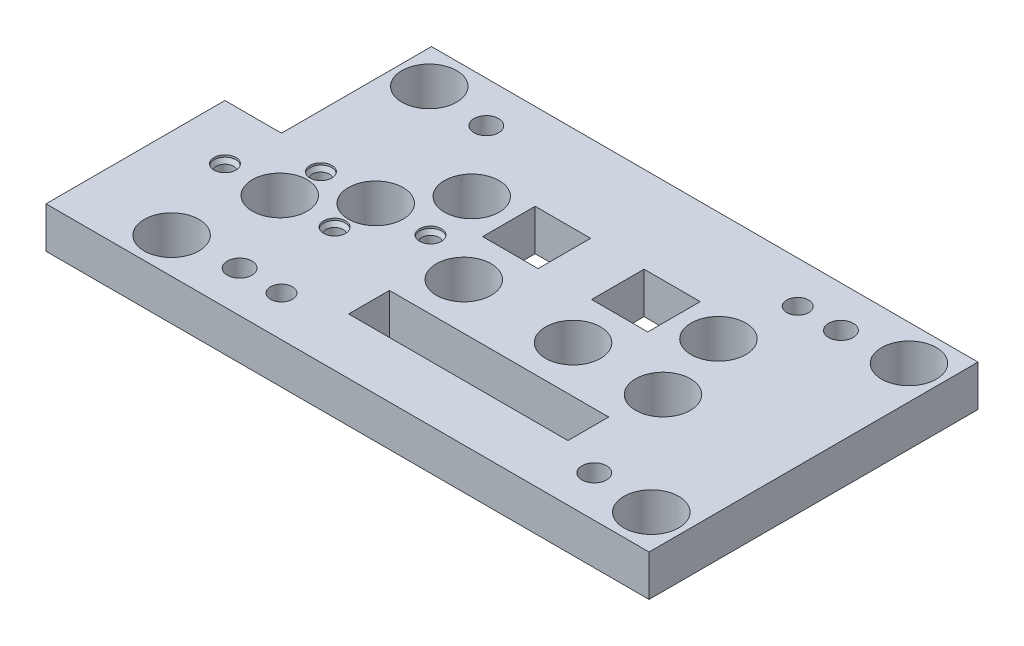
SolidWorks part; units mm, degrees
material "Plain Carbon Steel"
ref_plane "Front Plane" through (0, 0, 0) normal (0, 0, 1) x (1, 0, 0)
ref_plane "Top Plane" through (0, 0, 0) normal (0, 1, 0) x (1, 0, 0)
ref_plane "Right Plane" through (0, 0, 0) normal (1, 0, 0) x (0, 0, -1)
sketch "Sketch1" plane through (0, 0, 0) normal (0, 1, 0) x (1, 0, 0)
  line L1 (-110, -60) -> (110, -60)
  line L2 (-110, -60) -> (-110, 60)
  line L3 (-110, 60) -> (110, 60)
  line L4 (110, -60) -> (110, 60)
  line L5 (-110, -60) -> (110, 60) construction
  line L6 (-110, 60) -> (110, -60) construction
  point P0 (0, 0)
  dimension "D1" = 120
  dimension "D2" = 220
extrude "Boss-Extrude1" add sketch "Sketch1" against normal blind 15
sketch "Sketch2" plane through (0, 0, 0) normal (0, 1, 0) x (1, 0, 0)
  line L1 (-110, 60) -> (-89.3675, 60)
  line L2 (-110, 60) -> (-110, 5.27)
  line L3 (-110, 5.27) -> (-89.3675, 5.27)
  line L4 (-89.3675, 60) -> (-89.3675, 5.27)
  line L5 (-90, -14.72) -> (-89.3675, 5.27) construction
  line L10 (-70, 0.28) -> (-89.3675, 5.27) construction
  circle A0 centre (-70, 0.28) radius 3.1 construction
  circle A1 centre (-90, -14.72) radius 3.1 construction
  dimension "D1" = 20
extrude "Cut-Extrude1" cut sketch "Sketch2" against normal up to next
sketch "Sketch3" plane through (0, 0, 0) normal (0, 1, 0) x (1, 0, 0)
  line L0 (-20, 27.5) -> (-20, 9.28) construction
  line L1 (-20, 9.28) -> (0.25, 9.28) construction
  line L2 (0.25, 9.28) -> (0.25, 27.5) construction
  line L3 (19.75, 27.5) -> (19.75, 9.28) construction
  line L4 (19.75, 9.28) -> (40.25, 9.28) construction
  line L5 (40.25, 9.28) -> (40.25, 27.5) construction
  line L6 (-20, 28.44) -> (-20, 9.28)
  line L7 (-20, 9.28) -> (0.25, 9.28)
  line L8 (0.25, 9.28) -> (0.25, 28.44)
  line L9 (19.75, 28.44) -> (19.75, 9.28)
  line L10 (19.75, 9.28) -> (40.25, 9.28)
  line L11 (40.25, 9.28) -> (40.25, 28.44)
  line L12 (-20, 28.44) -> (0.25, 28.44)
  line L14 (19.75, 28.44) -> (40.25, 28.44)
  line L15 (0.31, 28.5) -> (-20.06, 28.5) construction
  dimension "D1" = 0.06
extrude "Cut-Extrude2" cut sketch "Sketch3" against normal up to next
sketch "Sketch4" plane through (0, 0, 0) normal (0, 1, 0) x (1, 0, 0)
  line L0 (-20.06, -39.66) -> (60.06, -39.66) construction
  line L1 (60, -24.72) -> (-20, -24.72)
  line L2 (60, -24.72) -> (60, -39.6)
  line L3 (60, -39.6) -> (-20, -39.6)
  line L4 (-20, -24.72) -> (-20, -39.6)
  dimension "D1" = 80
  dimension "D2" = 0.06
  dimension "D3" = 14.88
extrude "Cut-Extrude3" cut sketch "Sketch4" against normal up to next
hole_wizard "Ø6.2 (6.2) Diameter Hole1" positions "Sketch7" profile "Sketch6" hole size "Ø6.2" standard "ISO" end condition through all
sketch "Sketch7" plane through (0, 0, 0) normal (0, 1, 0) x (1, 0, 0)
  point P0 (-30, 0.28)
  point P3 (-50, -14.72)
  point P6 (-70, 0.28)
  point P9 (-90, -14.72)
sketch "Sketch6" plane through (-30, 0, -0.28) normal (1, 0, 0) x (0, 0, 1)
  line L0 (0, 0) -> (0, 15)
  line L1 (0, 15) -> (3.1, 15)
  line L2 (3.1, 15) -> (3.1, 0)
  line L5 (3.1, 0) -> (0, 0)
  line L11 (0, -6.35) -> (0, 107.95) construction
  dimension "Thru Hole Dia." = 6.2
  dimension "Thru Hole Depth" = 15
sketch "Sketch8" plane through (0, 0, 0) normal (0, 1, 0) x (1, 0, 0)
  circle A0 centre (-90, -14.72) radius 4
  circle A1 centre (-70, 0.28) radius 4
  circle A2 centre (-50, -14.72) radius 4
  circle A3 centre (-30, 0.28) radius 4
  dimension "D1" = 8
extrude "Cut-Extrude4" cut sketch "Sketch8" against normal blind 0.5
chamfer "Chamfer1" distance 1.8 angle 30 4 edges at (-90, -0.5, 17.82) (-30, -0.5, 2.82) (-50, -0.5, 17.82) (-70, -0.5, 2.82) first distance on face at (-90, -15, 17.82) first distance on face at (-30, -15, 2.82) first distance on face at (-50, -15, 17.82) first distance on face at (-70, -15, 2.82)
sketch "Sketch9" plane through (0, 0, 0) normal (0, 1, 0) x (1, 0, 0)
  circle A0 centre (-77.1837, -47) radius 10 construction
  circle A1 centre (97.8163, -47) radius 10 construction
  circle A2 centre (62.8163, -7.72) radius 10 construction
  circle A3 centre (30, -7.72) radius 10 construction
  circle A4 centre (-9.875, -7.72) radius 10 construction
  circle A5 centre (-70, -14.72) radius 10 construction
  circle A6 centre (-50, 0.28) radius 10 construction
  circle A7 centre (55.3163, 20) radius 10 construction
  circle A8 centre (97.8163, 47) radius 10 construction
  circle A12 centre (-34.6837, 20) radius 10 construction
  circle A13 centre (-77.1837, 47) radius 10 construction
  circle A14 centre (-77.1837, -47) radius 10
  circle A15 centre (97.8163, -47) radius 10
  circle A16 centre (62.8163, -7.72) radius 10
  circle A17 centre (30, -7.72) radius 10
  circle A18 centre (-9.875, -7.72) radius 10
  circle A19 centre (-70, -14.72) radius 10
  circle A20 centre (-50, 0.28) radius 10
  circle A21 centre (55.3163, 20) radius 10
  circle A22 centre (97.8163, 47) radius 10
  circle A26 centre (-34.6837, 20) radius 10
  circle A27 centre (-77.1837, 47) radius 10
extrude "Cut-Extrude5" cut sketch "Sketch9" against normal up to next
hole_wizard "CBORE for M8 Hex Socket Head Cap Screw1" positions "Sketch12" profile "Sketch11" counterbore size "M8" standard "ISO" end condition through all
sketch "Sketch12" plane through (0, -15, 0) normal (0, -1, 0) x (-1, 0, 0)
  line L0 (-110, -60) -> (-110, 60) construction
  line L1 (-110, 60) -> (89.3675, 60) construction
  line L3 (89.3675, 5.27) -> (89.3675, 60) construction
  line L4 (110, -60) -> (-110, -60) construction
  point P4 (-75, 45)
  point P6 (54.3675, 45)
  point P8 (54.3675, -45)
  point P10 (-75, -45)
  point P21 (0, 0)
  point P26 (0, 0)
  point P27 (0, 0)
  point P28 (0, 0)
  dimension "D1" = 35
  dimension "D2" = 15
  dimension "D3" = 35
  dimension "D4" = 15
sketch "Sketch11" plane through (75, -15, -45) normal (1, 0, 0) x (0, 0, -1)
  line L0 (0, 0) -> (0, 15)
  line L1 (0, 15) -> (4.5, 15)
  line L3 (4.5, 15) -> (4.5, 8.6)
  line L4 (4.5, 8.6) -> (7.5, 8.6)
  line L5 (7.5, 8.6) -> (7.5, 0)
  line L7 (7.5, 0) -> (0, 0)
  line L11 (0, -6.35) -> (0, 107.95) construction
  dimension "Thru Hole Dia." = 9
  dimension "Thru Hole Depth" = 15
  dimension "C'Bore Dia." = 15
  dimension "C'Bore Depth" = 8.6
hole_wizard "Ø8.0mm Dowel Hole1" positions "Sketch15" profile "Sketch14" hole size "Ø8.0" standard "ISO" end condition through all
sketch "Sketch15" plane through (0, -15, 0) normal (0, -1, 0) x (-1, 0, 0)
  circle A0 centre (-75, 45) radius 7.5 construction
  circle A1 centre (54.3675, -45) radius 7.5 construction
  point P0 (-59.5, 44.7284)
  point P4 (38.8675, -45.241)
  dimension "D1" = 8
  dimension "D2" = 8
sketch "Sketch14" plane through (59.5, -15, -44.7284) normal (1, 0, 0) x (0, 0, -1)
  line L0 (0, 0) -> (0, 15)
  line L1 (0, 15) -> (4, 15)
  line L2 (4, 15) -> (4, 0)
  line L5 (4, 0) -> (0, 0)
  line L11 (0, -6.35) -> (0, 107.95) construction
  dimension "Thru Hole Dia." = 8
  dimension "Thru Hole Depth" = 15
